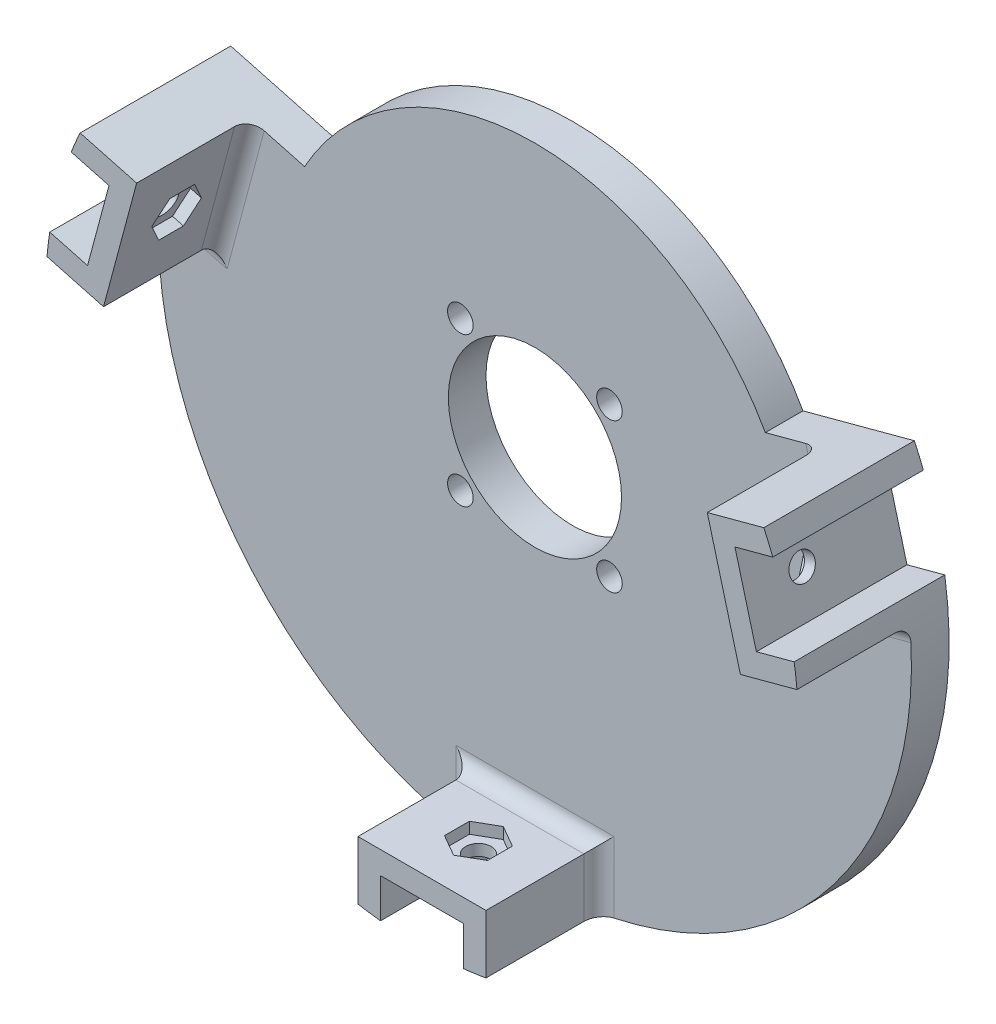
SolidWorks part; units mm, degrees
ref_plane "前视基准面" through (0, 0, 0) normal (0, 0, 1) x (1, 0, 0)
ref_plane "上视基准面" through (0, 0, 0) normal (0, 1, 0) x (1, 0, 0)
ref_plane "右视基准面" through (0, 0, 0) normal (1, 0, 0) x (0, 0, -1)
ref_plane "基准面4" through (0, 300, 0) normal (0, -1, 0) x (1, 0, 0)
sketch "草图1" plane through (0, 300, 0) normal (0, -1, 0) x (1, 0, 0)
  line L0 (950, 5) -> (900, 5)
  line L1 (900, 5) -> (900, 0)
  line L2 (900, 0) -> (950, 0)
  line L3 (950, 0) -> (950, 5)
  line L4 (900, 5) -> (900, 0) construction
revolve "旋转1" add sketch "草图1" angle 360 about L4 reverse direction yes
sketch "草图2" plane through (0, 0, 5) normal (0, 0, 1) x (1, 0, 0)
  line L0 (854.6067, 320.963) -> (869.4047, 316.9978)
  line L1 (930.5953, 316.9978) -> (945.3933, 320.963)
  arc A0 (945.3933, 320.963) -> (854.6067, 320.963) centre (900, 300) ccw
  arc A1 (869.4047, 316.9978) -> (930.5953, 316.9978) centre (900, 300) cw
extrude "切除-拉伸1" cut sketch "草图2" against normal through all
sketch "草图3" plane through (0, 0, 5) normal (0, 0, 1) x (1, 0, 0)
  line L0 (854.6067, 320.963) -> (862.114, 318.9514)
  line L1 (862.114, 318.9514) -> (857.7141, 302.5306)
  line L2 (857.7141, 302.5306) -> (850.2067, 304.5422)
  arc A0 (850.2067, 304.5422) -> (854.6067, 320.963) centre (900, 300) cw
extrude "凸台-拉伸1" add sketch "草图3" along normal blind 15
sketch "草图4" plane through (0, 0, 20) normal (0, 0, 1) x (1, 0, 0)
  line L0 (850.5733, 307.5498) -> (855.5928, 306.2049)
  line L1 (855.5928, 306.2049) -> (858.4398, 316.83)
  line L2 (858.4398, 316.83) -> (853.4203, 318.175)
  arc A0 (853.4203, 318.175) -> (850.5733, 307.5498) centre (900, 300) ccw
extrude "切除-拉伸2" cut sketch "草图4" against normal through all
sketch "草图5" plane through (0, 0, 5) normal (0, 0, 1) x (1, 0, 0)
  line L0 (891.5, 250.7278) -> (891.5, 258.5)
  line L1 (891.5, 258.5) -> (908.5, 258.5)
  line L2 (908.5, 258.5) -> (908.5, 250.7278)
  arc A0 (908.5, 250.7278) -> (891.5, 250.7278) centre (900, 300) cw
extrude "凸台-拉伸2" add sketch "草图5" along normal blind 15
sketch "草图6" plane through (0, 0, 20) normal (0, 0, 1) x (1, 0, 0)
  line L0 (905.5, 250.3034) -> (905.5, 255.5)
  line L1 (905.5, 255.5) -> (894.5, 255.5)
  line L2 (894.5, 255.5) -> (894.5, 250.3034)
  arc A0 (894.5, 250.3034) -> (905.5, 250.3034) centre (900, 300) ccw
extrude "切除-拉伸3" cut sketch "草图6" against normal through all
sketch "草图7" plane through (0, 0, 5) normal (0, 0, 1) x (1, 0, 0)
  line L0 (949.7933, 304.5422) -> (942.2859, 302.5306)
  line L1 (942.2859, 302.5306) -> (937.886, 318.9514)
  line L2 (937.886, 318.9514) -> (945.3933, 320.963)
  arc A0 (945.3933, 320.963) -> (949.7933, 304.5422) centre (900, 300) cw
extrude "凸台-拉伸3" add sketch "草图7" along normal blind 15
sketch "草图8" plane through (0, 0, 20) normal (0, 0, 1) x (1, 0, 0)
  line L0 (946.5797, 318.175) -> (941.5602, 316.83)
  line L1 (941.5602, 316.83) -> (944.4072, 306.2049)
  line L2 (944.4072, 306.2049) -> (949.4267, 307.5498)
  arc A0 (949.4267, 307.5498) -> (946.5797, 318.175) centre (900, 300) ccw
extrude "切除-拉伸4" cut sketch "草图8" against normal through all
sketch "草图9" plane through (0, 258.5, 0) normal (0, 1, 0) x (-1, 0, 0)
  line L0 (-902.8579, 14.15) -> (-902.8579, 10.85)
  line L1 (-902.8579, 10.85) -> (-900, 9.2)
  line L2 (-900, 9.2) -> (-897.1421, 10.85)
  line L3 (-897.1421, 10.85) -> (-897.1421, 14.15)
  line L4 (-897.1421, 14.15) -> (-900, 15.8)
  line L5 (-900, 15.8) -> (-902.8579, 14.15)
extrude "切除-拉伸5" cut sketch "草图9" against normal blind 1.5
sketch "草图10" plane through (724.6255, -194.1628, 0) normal (0.9659, -0.2588, 0) x (0, 0, -1)
  line L0 (-14.15, 519.857) -> (-10.85, 519.857)
  line L1 (-10.85, 519.857) -> (-9.2, 522.7149)
  line L2 (-9.2, 522.7149) -> (-10.85, 525.5728)
  line L3 (-10.85, 525.5728) -> (-14.15, 525.5728)
  line L4 (-14.15, 525.5728) -> (-15.8, 522.7149)
  line L5 (-15.8, 522.7149) -> (-14.15, 519.857)
extrude "切除-拉伸6" cut sketch "草图10" against normal blind 1.5
sketch "草图11" plane through (954.7974, 255.8372, 0) normal (-0.9659, -0.2588, 0) x (0, 0, 1)
  line L0 (10.85, 59.6985) -> (9.2, 56.8406)
  line L1 (9.2, 56.8406) -> (10.85, 53.9827)
  line L2 (10.85, 53.9827) -> (14.15, 53.9827)
  line L3 (14.15, 53.9827) -> (15.8, 56.8406)
  line L4 (15.8, 56.8406) -> (14.15, 59.6985)
  line L5 (14.15, 59.6985) -> (10.85, 59.6985)
extrude "切除-拉伸7" cut sketch "草图11" against normal blind 1.5
hole_wizard "Ø23.0 (23) 直径孔1" positions "草图13" profile "草图12" hole size "Ø23.0" standard "ANSI Metric"
sketch "草图13" plane through (0, 0, 0) normal (0, 0, -1) x (-1, 0, 0)
  point P0 (-900, 300)
sketch "草图12" plane through (900, 300, 0) normal (1, 0, 0) x (0, 1, 0)
  line L0 (0, 0) -> (0, 20)
  line L1 (0, 20) -> (11.5, 20)
  line L2 (11.5, 20) -> (11.5, 0)
  line L5 (11.5, 0) -> (0, 0)
  line L11 (0, -6.35) -> (0, 107.95) construction
  dimension "通孔孔直径" = 23
  dimension "通孔孔深度" = 20
hole_wizard "Ø3.4 (3.4) 直径孔1" positions "草图15" profile "草图14" hole size "Ø3.4" standard "ANSI Metric"
sketch "草图15" plane through (0, 0, 0) normal (0, 0, -1) x (-1, 0, 0)
  point P0 (-909.8995, 290.1005)
  point P1 (-909.8995, 309.8995)
  point P2 (-890.1005, 309.8995)
  point P3 (-890.1005, 290.1005)
sketch "草图14" plane through (909.8995, 290.1005, 0) normal (1, 0, 0) x (0, 1, 0)
  line L0 (0, 0) -> (0, 20)
  line L1 (0, 20) -> (1.7, 20)
  line L2 (1.7, 20) -> (1.7, 0)
  line L5 (1.7, 0) -> (0, 0)
  line L11 (0, -6.35) -> (0, 107.95) construction
  dimension "通孔孔直径" = 3.4
  dimension "通孔孔深度" = 20
hole_wizard "Ø3.4 (3.4) 直径孔2" positions "草图17" profile "草图16" hole size "Ø3.4" standard "ANSI Metric"
sketch "草图17" plane through (0, 257, 0) normal (0, 1, 0) x (1, 0, 0)
  point P0 (900, -12.5)
sketch "草图16" plane through (900, 257, 12.5) normal (1, 0, 0) x (0, 0, 1)
  line L0 (0, 0) -> (0, 6.6966)
  line L1 (0, 6.6966) -> (1.7, 6.6966)
  line L2 (1.7, 6.6966) -> (1.7, 0)
  line L5 (1.7, 0) -> (0, 0)
  line L11 (0, -6.35) -> (0, 107.95) construction
  dimension "通孔孔直径" = 3.4
  dimension "通孔孔深度" = 6.6966
hole_wizard "Ø3.4 (3.4) 直径孔3" positions "草图19" profile "草图18" hole size "Ø3.4" standard "ANSI Metric"
sketch "草图19" plane through (723.1766, -193.7746, 0) normal (0.9659, -0.2588, 0) x (0, 0, -1)
  point P0 (-12.5, 522.7149)
sketch "草图18" plane through (858.4652, 311.1292, 12.5) normal (0, 0, 1) x (0.2588, 0.9659, 0)
  line L0 (0, 0) -> (0, 14.355)
  line L1 (0, 14.355) -> (1.7, 14.355)
  line L2 (1.7, 14.355) -> (1.7, 0)
  line L5 (1.7, 0) -> (0, 0)
  line L11 (0, -6.35) -> (0, 107.95) construction
  dimension "通孔孔直径" = 3.4
  dimension "通孔孔深度" = 14.355
hole_wizard "Ø3.4 (3.4) 直径孔4" positions "草图21" profile "草图20" hole size "Ø3.4" standard "ANSI Metric"
sketch "草图21" plane through (956.2462, 256.2254, 0) normal (-0.9659, -0.2588, 0) x (0, 0, 1)
  point P0 (12.5, 56.8406)
sketch "草图20" plane through (941.5348, 311.1292, 12.5) normal (0, 0, 1) x (0.2588, -0.9659, 0)
  line L0 (0, 0) -> (0, 14.355)
  line L1 (0, 14.355) -> (1.7, 14.355)
  line L2 (1.7, 14.355) -> (1.7, 0)
  line L5 (1.7, 0) -> (0, 0)
  line L11 (0, -6.35) -> (0, 107.95) construction
  dimension "通孔孔直径" = 3.4
  dimension "通孔孔深度" = 14.355
fillet "圆角1" radius 2 7 edges at (859.9141, 310.741, 5) (853.9604, 303.5364, 5) (908.5, 254.6139, 5) (900, 258.5, 5) (891.5, 254.6139, 5) (940.0859, 310.741, 5) (946.0396, 303.5364, 5)
